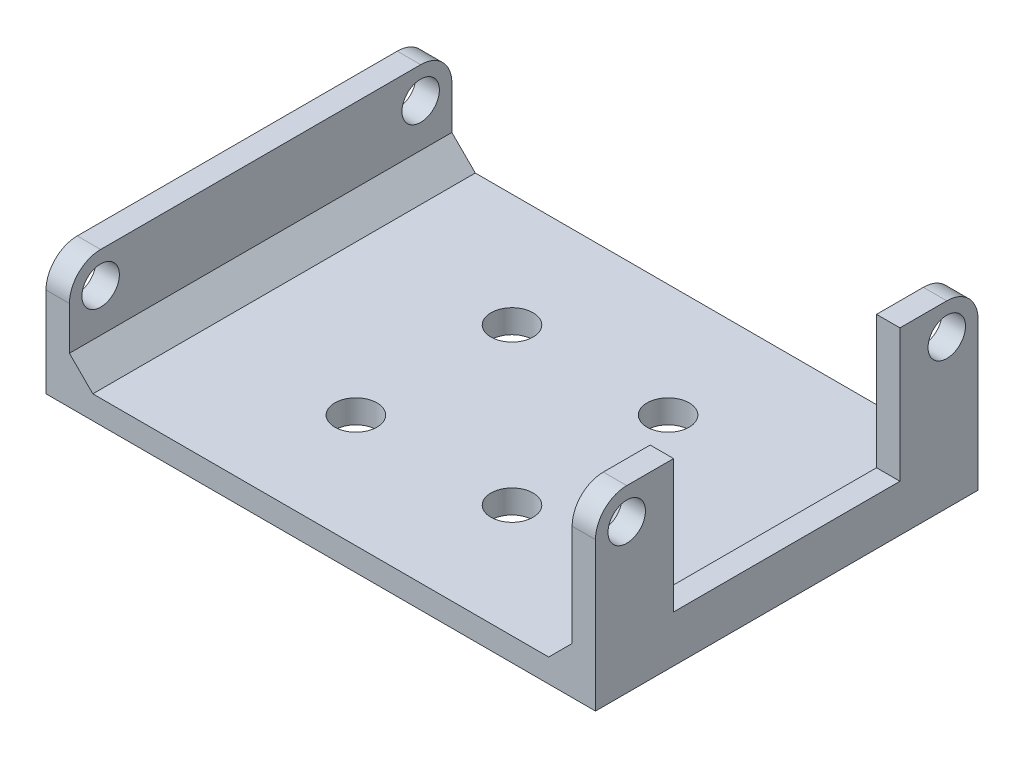
SolidWorks part; units mm, degrees
ref_plane "Front Plane" through (0, 0, 0) normal (0, 0, 1) x (1, 0, 0)
ref_plane "Top Plane" through (0, 0, 0) normal (0, 1, 0) x (1, 0, 0)
ref_plane "Right Plane" through (0, 0, 0) normal (1, 0, 0) x (0, 0, -1)
sketch "Sketch1" plane through (0, 0, 0) normal (0, 1, 0) x (1, 0, 0)
  line L0 (0, 0) -> (-50000, 0) construction
  line L1 (17.6, -12.25) -> (-17.6, -12.25)
  line L2 (17.6, -12.25) -> (17.6, 12.25)
  line L3 (17.6, 12.25) -> (-17.6, 12.25)
  line L4 (-17.6, -12.25) -> (-17.6, 12.25)
  line L5 (17.6, -12.25) -> (-17.6, 12.25) construction
  line L6 (17.6, 12.25) -> (-17.6, -12.25) construction
  line L7 (5, -5) -> (-5, -5) construction
  line L8 (5, -5) -> (5, 5) construction
  line L9 (5, 5) -> (-5, 5) construction
  line L10 (-5, -5) -> (-5, 5) construction
  line L11 (5, -5) -> (-5, 5) construction
  line L12 (5, 5) -> (-5, -5) construction
  line L13 (0, 0) -> (0, 50000) construction
  circle A0 centre (-5, 5) radius 1.35
  circle A1 centre (5, 5) radius 1.35
  circle A2 centre (-5, -5) radius 1.35
  circle A3 centre (5, -5) radius 1.35
  point P0 (0, 0)
  point P6 (0, 0)
  point P14 (-17.6, 0)
  dimension "D5" = 2.7
  dimension "D1" = 35.2
  dimension "D2" = 24.5
  dimension "D3" = 10
  dimension "D4" = 10
extrude "Boss-Extrude1" add sketch "Sketch1" along normal blind 1.5
sketch "Sketch2" plane through (17.6, 0, 0) normal (1, 0, 0) x (0, 0, -1)
  line L0 (-7.25, 0) -> (-7.25, 11.51)
  line L1 (-12.25, 0) -> (12.25, 0) construction
  line L2 (-7.25, 0) -> (-12.25, 0)
  line L3 (-7.25, 11.51) -> (-10.25, 11.51)
  line L4 (-12.25, 9.51) -> (-12.25, 0)
  line L5 (-9.05, 9.51) -> (-7.25, 9.51) construction
  line L6 (-10.25, 10.71) -> (-10.25, 11.51) construction
  line L7 (0, 0) -> (0, 50000) construction
  line L8 (10.25, 10.71) -> (10.25, 11.51) construction
  line L9 (9.05, 9.51) -> (7.25, 9.51) construction
  line L10 (12.25, 9.51) -> (12.25, 0)
  line L11 (7.25, 11.51) -> (10.25, 11.51)
  line L12 (7.25, 0) -> (12.25, 0)
  line L13 (7.25, 0) -> (7.25, 11.51)
  line L14 (-7.25, 3) -> (7.25, 3)
  line L15 (-7.25, 0) -> (7.25, 0)
  line L17 (-12.25, 1.5) -> (12.25, 1.5) construction
  circle A0 centre (-10.25, 9.51) radius 1.2
  arc A1 (-10.25, 11.51) -> (-12.25, 9.51) centre (-10.25, 9.51) ccw
  arc A2 (10.25, 11.51) -> (12.25, 9.51) centre (10.25, 9.51) cw
  circle A3 centre (10.25, 9.51) radius 1.2
  line M10 (-12.25, 0) -> (12.25, 0)
  line M11 (12.25, 0) -> (12.25, 1.5)
  line M12 (12.25, 1.5) -> (-12.25, 1.5)
  line M13 (-12.25, 1.5) -> (-12.25, 0)
  dimension "D3" = 2.4
  dimension "D1" = 11.51
  dimension "D2" = 5
  dimension "D4" = 1.8
  dimension "D5" = 0.8
  dimension "D6" = 1.5
extrude "Boss-Extrude2" add sketch "Sketch2" against normal blind 1.5 contours L3 A1 L4 L0 A0 M12 | L0 M10 M12 M13 | L13 L0 M10 M12 | L14 L0 L13 M12 | L13 M10 M11 M12 | A2 L11 L13 L10 A3 M12 region at (17.6, 6.1131, 9.6599) region at (17.6, 2.25, 0) region at (17.6, 0.75, 0) region at (17.6, 0.75, 9.75) region at (17.6, 6.1131, -9.6599) region at (17.6, 0.75, -9.75)
sketch "Sketch3" plane through (-17.6, 0, 0) normal (-1, 0, 0) x (0, 0, 1)
  line L0 (-12.25, 0) -> (12.25, 0)
  line L3 (10.25, 7.76) -> (-10.25, 7.76)
  line L4 (0, 7.76) -> (0, 0) construction
  line L5 (-12.25, 5.76) -> (-12.25, 0)
  line L6 (-10.25, 6.96) -> (-10.25, 7.76) construction
  line L7 (-11.45, 5.76) -> (-12.25, 5.76) construction
  line L8 (11.45, 5.76) -> (12.25, 5.76) construction
  line L9 (10.25, 6.96) -> (10.25, 7.76) construction
  line L10 (12.25, 5.76) -> (12.25, 0)
  circle A0 centre (-10.25, 5.76) radius 1.2
  arc A1 (-10.25, 7.76) -> (-12.25, 5.76) centre (-10.25, 5.76) ccw
  arc A2 (10.25, 7.76) -> (12.25, 5.76) centre (10.25, 5.76) cw
  circle A3 centre (10.25, 5.76) radius 1.2
  dimension "D2" = 2.4
  dimension "D1" = 7.76
  dimension "D3" = 0.8
  dimension "D4" = 0.8
extrude "Boss-Extrude3" add sketch "Sketch3" against normal blind 1.5
chamfer "Chamfer1" distance 1.5 angle 45 2 edges at (-16.1, 1.5, 0) (16.1, 1.5, 0)
